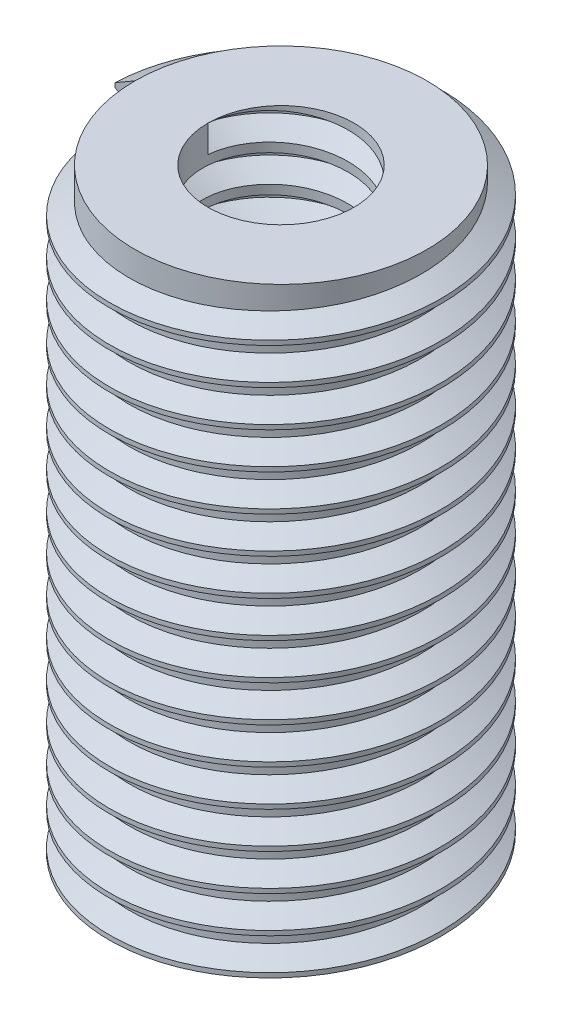
SolidWorks part; units mm, degrees
ref_plane "Front Plane" through (0, 0, 0) normal (0, 0, 1) x (1, 0, 0)
ref_plane "Top Plane" through (0, 0, 0) normal (0, 1, 0) x (1, 0, 0)
ref_plane "Right Plane" through (0, 0, 0) normal (1, 0, 0) x (0, 0, -1)
sketch "Sketch1" plane through (0, 0, 0) normal (0, 1, 0) x (1, 0, 0)
  circle A0 centre (0, 0) radius 5
  dimension "D1" = 10
extrude "Boss-Extrude1" add sketch "Sketch1" along normal blind 20
sketch "Sketch2" plane through (0, 20, 0) normal (0, 1, 0) x (1, 0, 0)
  circle A0 centre (0, 0) radius 2.5
  dimension "D1" = 5
extrude "Cut-Extrude1" cut sketch "Sketch2" against normal through all
thread "Thread1" pitch 1.25 method cut profile "Thread Profile1" start angle 0, offset 0, length 20, pitch 1.25, diameter 5
ref_plane "Plane1" through (-2.5, 20, 0) normal (0, 0, 1) x (-1, 0, 0)
sketch "Thread Profile1" plane through (-2.5, 20, 0) normal (0, 0, 1) x (-1, 0, 0)
  line L0 (0, 0) -> (0, 1.25) construction
  line L1 (0, 0) -> (0.6766, 0.3906)
  line L2 (0.6766, 0.3906) -> (0.6766, 0.5469)
  line L3 (0.6766, 0.5469) -> (0, 0.9375)
  line L4 (0.6766, 0.4687) -> (0, 0.4687) construction
  line L11 (0, 0) -> (0, 0.9375)
  point P2 (0, 0)
  dimension "Pitch" = 1.25
  dimension "Profile_Angle" = 60
  dimension "Profile_Land" = 0.1562
  dimension "Profile_Height" = 0.6766
thread "Thread2" pitch 1.25 method extrude profile "Thread Profile2" start angle 0, offset 0, length 20, pitch 1.25, diameter 10
ref_plane "Plane2" through (-5, 20, 0) normal (0, 0, 1) x (-1, 0, 0)
sketch "Thread Profile2" plane through (-5, 20, 0) normal (0, 0, 1) x (-1, 0, 0)
  line L0 (0, 0) -> (0, 1.25) construction
  line L1 (0, 0) -> (0.6766, 0.3906)
  line L2 (0.6766, 0.3906) -> (0.6766, 0.5469)
  line L3 (0.6766, 0.5469) -> (0, 0.9375)
  line L4 (0.6766, 0.4687) -> (0, 0.4687) construction
  line L11 (0, 0) -> (0, 0.9375)
  point P2 (0, 0)
  dimension "Pitch" = 1.25
  dimension "Profile_Angle" = 60
  dimension "Profile_Land" = 0.1562
  dimension "Profile_Height" = 0.6766
